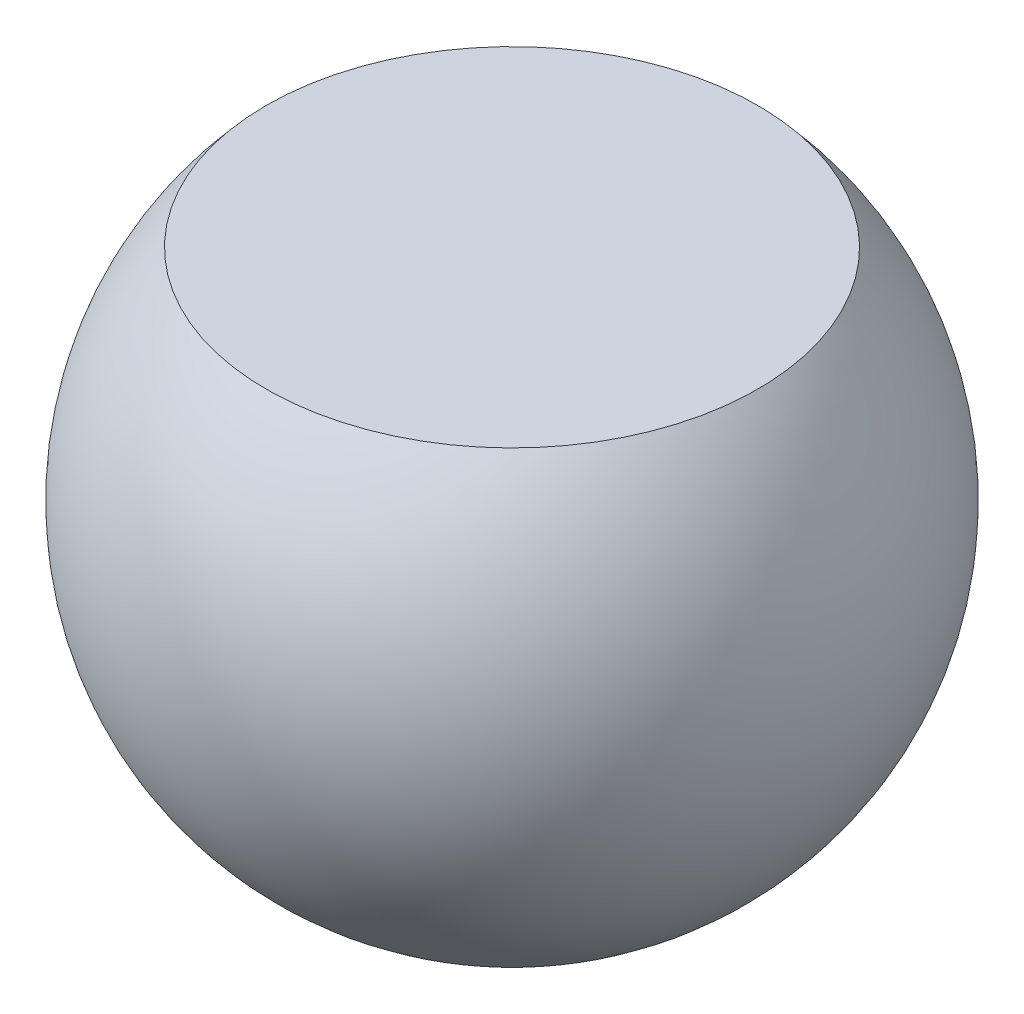
SolidWorks part; units mm, degrees
ref_plane "前视基准面" through (0, 0, 0) normal (0, 0, 1) x (1, 0, 0)
ref_plane "上视基准面" through (0, 0, 0) normal (0, 1, 0) x (1, 0, 0)
ref_plane "右视基准面" through (0, 0, 0) normal (1, 0, 0) x (0, 0, -1)
sketch "草图1" plane through (0, 0, 0) normal (0, 0, 1) x (1, 0, 0)
  line L0 (0, 6) -> (6.7082, 6)
  line L1 (0, 6) -> (0, -9)
  arc A0 (0, -9) -> (6.7082, 6) centre (0, 0) ccw
  dimension "D1" = 18
  dimension "D2" = 6
revolve "旋转1" add sketch "草图1" angle 360 about L1
